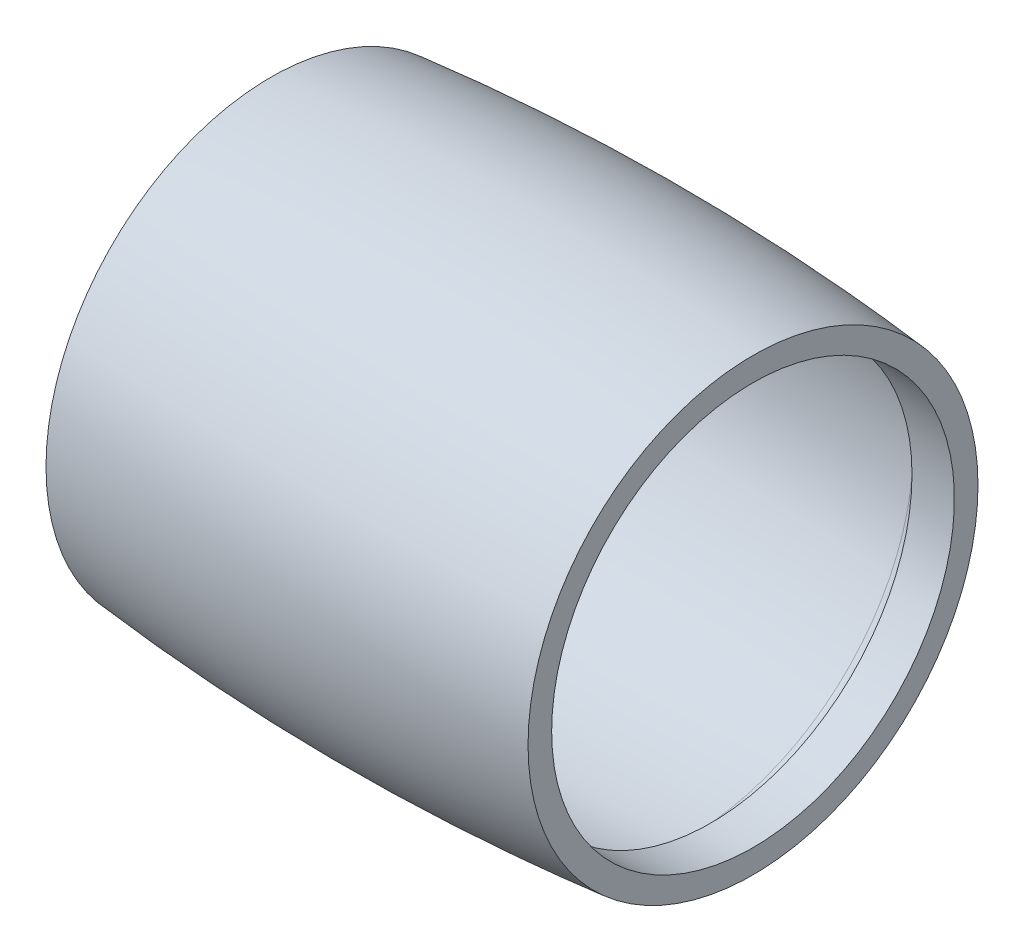
SolidWorks part; units mm, degrees
ref_plane "Front Plane" through (0, 0, 0) normal (0, 0, 1) x (1, 0, 0)
ref_plane "Top Plane" through (0, 0, 0) normal (0, 1, 0) x (1, 0, 0)
ref_plane "Right Plane" through (0, 0, 0) normal (1, 0, 0) x (0, 0, -1)
sketch "Sketch1" plane through (0, 0, 0) normal (0, 0, 1) x (1, 0, 0)
  line L0 (-40.815, 0) -> (40.815, 0) construction
  line L1 (-40.815, 0) -> (-40.815, 38.1)
  line L2 (40.815, 0) -> (40.815, 38.1)
  line L3 (0, 0) -> (0, 40.1) construction
  line L19 (-33.64, 0) -> (-33.64, 37.7391)
  line L20 (33.64, 0) -> (33.64, 37.7391)
  line L21 (-40.815, 0) -> (-33.64, 0)
  line L22 (33.64, 0) -> (40.815, 0)
  arc A0 (-40.815, 38.1) -> (40.815, 38.1) centre (0, -377.3661) cw
  arc A1 (-33.64, 37.7391) -> (33.64, 37.7391) centre (0, -377.3661) cw
  dimension "D1" = 38.1
  dimension "D3" = 1
  dimension "D5" = 81.63
  dimension "D2" = 7.175
  dimension "D4" = 2
revolve "Revolve2" add sketch "Sketch1" angle 360 about L0
sketch "Sketch2" plane through (-40.815, 0, 0) normal (-1, 0, 0) x (0, 0, 1)
  circle A38 centre (0, 0) radius 34.1
  circle A39 centre (0, 0) radius 38.1 construction
  dimension "D1" = 4
extrude "Cut-Extrude1" cut sketch "Sketch2" against normal through all both and the other way through all
fillet "Fillet2" radius 4 2 edges at (33.64, 0, 37.7391) (-33.64, 0, 37.7391)
equation "\"SpokeWidth\"= 5"
equation "\"HubDiameter\"= 30"
equation "\"PulleyDiameter\"= 3in"
equation "\"D1@Sketch1\"=\"PulleyDiameter\"/2"
equation "\"PulleyWidth\"= 3.45in"
equation "\"RimWidth\"= 5"
equation "\"D5@Sketch1\"=\"PulleyWidth\"-6"
